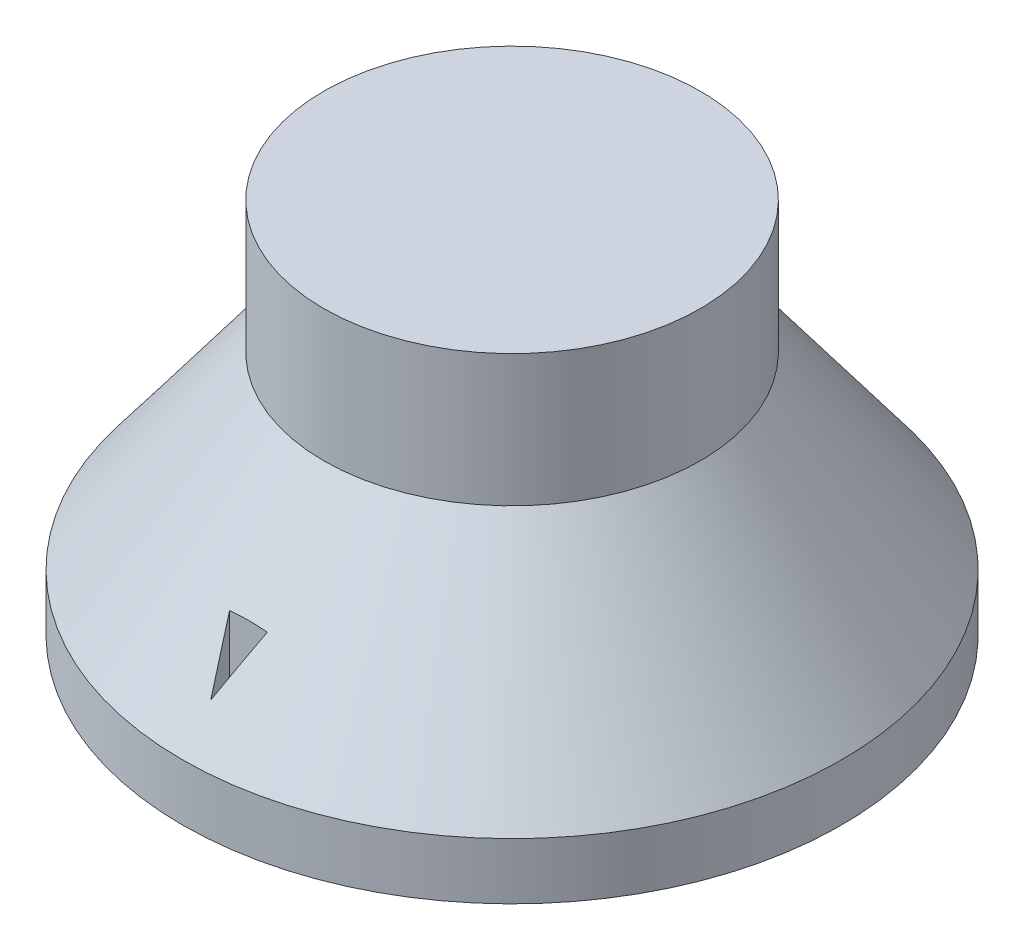
SolidWorks part; units mm, degrees
material "ABS"
ref_plane "Front Plane" through (0, 0, 0) normal (0, 0, 1) x (1, 0, 0)
ref_plane "Top Plane" through (0, 0, 0) normal (0, 1, 0) x (1, 0, 0)
ref_plane "Right Plane" through (0, 0, 0) normal (1, 0, 0) x (0, 0, -1)
sketch "Sketch1" plane through (0, 0, 0) normal (0, 1, 0) x (1, 0, 0)
  circle A0 centre (0, 0) radius 12.7
  dimension "D1" = 25.4
extrude "Boss-Extrude1" add sketch "Sketch1" along normal blind 8.89 contours A0
ref_plane "Plane1" through (0, -16.51, 0) normal (0, 1, 0) x (1, 0, 0)
sketch "Sketch2" plane through (0, -16.51, 0) normal (0, 1, 0) x (1, 0, 0)
  circle A0 centre (0, 0) radius 22.225
  dimension "D1" = 44.45
extrude "Boss-Extrude3" add sketch "Sketch2" along normal blind 3.81 separate body contours A0
loft "Loft2" add section edge at (0, 0, 12.7) section edge at (0, -12.7, 22.225) connector at (-7.4131, 0, 10.3119) connector at (-11.5649, -12.7, 18.9791)
sketch "Sketch3" plane through (0, -16.51, 0) normal (0, 1, 0) x (1, 0, 0)
  line L0 (0, 0) -> (0, -15.1036) construction
  line L1 (0, 0) -> (15.3422, 0) construction
  line L2 (0, 3.175) -> (4.7797, 5.9346)
  line L3 (0, 3.175) -> (-4.7797, 5.9346)
  line L4 (2.7496, -1.5875) -> (2.7496, -7.1066)
  line L5 (2.7496, -1.5875) -> (7.5293, 1.1721)
  line L6 (-2.7496, -1.5875) -> (-7.5293, 1.1721)
  line L7 (-2.7496, -1.5875) -> (-2.7496, -7.1066)
  arc A0 (4.7797, 5.9346) -> (-4.7797, 5.9346) centre (0, 0) ccw
  circle A1 centre (0, 0) radius 3.175
  arc A2 (2.7496, -7.1066) -> (7.5293, 1.1721) centre (0, 0) ccw
  arc A3 (-7.5293, 1.1721) -> (-2.7496, -7.1066) centre (0, 0) ccw
  point P19 (0, 0)
  dimension "D1" = 15.24
  dimension "D2" = 6.35
  dimension "D3" = 120
  dimension "D4" = 3
sketch "Sketch4" plane through (0, -16.51, 0) normal (0, 1, 0) x (1, 0, 0)
  circle A0 centre (0, 0) radius 7.62
extrude "Cut-Extrude2" cut sketch "Sketch4" along normal blind 3.81
extrude "Boss-Extrude4" add sketch "Sketch3" along normal blind 3.81 and the other way blind 6.35 contours L6 A3 L7 | L3 A0 L2 | L5 A2 L4
sketch "Sketch7" plane through (0, -12.7, 0) normal (0, -1, 0) x (1, 0, 0)
  circle A0 centre (0, 0) radius 3.175
extrude "Cut-Extrude3" cut sketch "Sketch7" against normal blind 12.7
sketch "Sketch9" plane through (0, 0, 0) normal (0, 1, 0) x (1, 0, 0)
  line L0 (0, -20.32) -> (1.27, -17.78)
  line L1 (1.27, -17.78) -> (-1.27, -17.78)
  line L2 (-1.27, -17.78) -> (0, -20.32)
  dimension "D1" = 20.32
  dimension "D2" = 2.54
  dimension "D3" = 2.54
extrude "Cut-Extrude4" cut sketch "Sketch9" against normal blind 12.7
